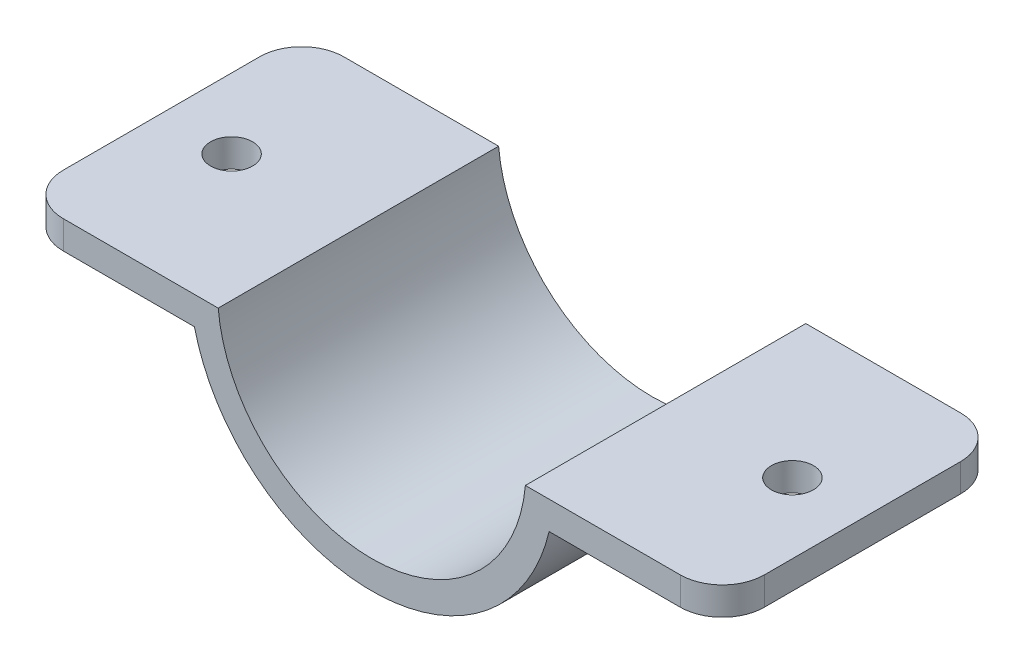
SolidWorks part; units mm, degrees
ref_plane "Front Plane" through (0, 0, 0) normal (0, 0, 1) x (1, 0, 0)
ref_plane "Top Plane" through (0, 0, 0) normal (0, 1, 0) x (1, 0, 0)
ref_plane "Right Plane" through (0, 0, 0) normal (1, 0, 0) x (0, 0, -1)
sketch "Sketch1" plane through (0, 0, 0) normal (0, 0, 1) x (1, 0, 0)
  line L0 (-25, -1) -> (25, -1)
  line L1 (25, -1) -> (25, -3)
  line L2 (25, -3) -> (12.6491, -3)
  line L3 (-25, -1) -> (-25, -3)
  line L4 (-25, -3) -> (-12.6491, -3)
  circle A0 centre (0, 0) radius 13
  circle A1 centre (0, 0) radius 11
  point P10 (0, -1)
  point P11 (0, 0)
  dimension "D2" = 22
  dimension "D3" = 2
  dimension "D1" = 50
  dimension "D4" = 2
  dimension "D5" = 1
extrude "Boss-Extrude1" add sketch "Sketch1" along normal blind 20 contours A1 L0 A0 | A0 L0 L3 L4 | A0 L2 L1 L0 region at (-18.9156, -2.0043, 0) region at (-11.958, -1.2857, 0) region at (18.9156, -2.0043, 0)
sketch "Sketch2" plane through (0, -3, 0) normal (0, -1, 0) x (1, 0, 0)
  line L1 (-25, 20) -> (-25, 0) construction
  line L2 (-25, 20) -> (-25, 0) construction
  circle A0 centre (-20, 10) radius 1.5
  point P6 (-25, 10)
  dimension "D1" = 3
  dimension "D2" = 5
extrude "Cut-Extrude1" cut sketch "Sketch2" against normal blind 20
mirror "Mirror1" about plane through (0, 0, 0) normal (1, 0, 0) of "Cut-Extrude1"
fillet "Fillet1" radius 3 4 edges at (25, -2, 0) (25, -2, 20) (-25, -2, 20) (-25, -2, 0)
